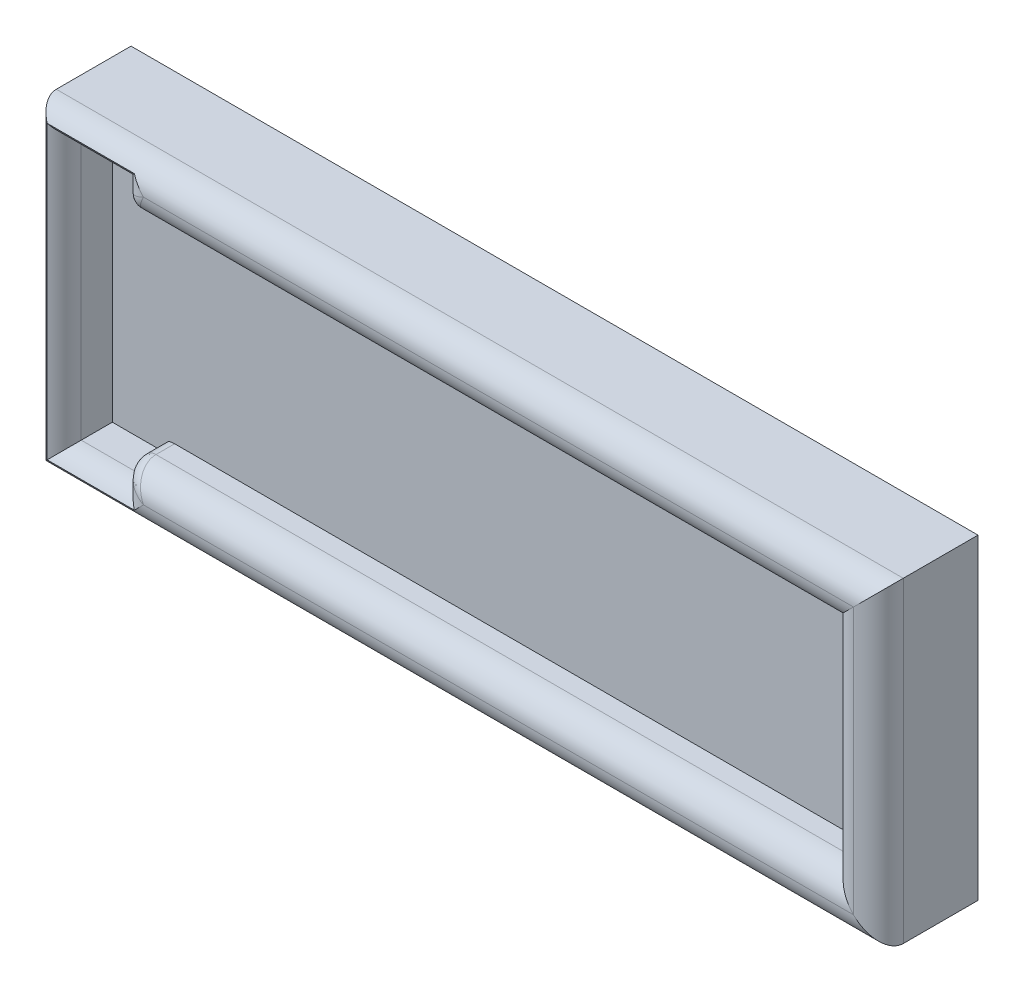
SolidWorks part; units mm, degrees
ref_plane "Спереди" through (0, 0, 0) normal (0, 0, 1) x (1, 0, 0)
ref_plane "Сверху" through (0, 0, 0) normal (0, 1, 0) x (1, 0, 0)
ref_plane "Справа" through (0, 0, 0) normal (1, 0, 0) x (0, 0, -1)
sketch "Эскиз1" plane through (0, 0, 0) normal (0, 0, 1) x (1, 0, 0)
  line L1 (17, -6.35) -> (-17, -6.35)
  line L2 (17, -6.35) -> (17, 6.35)
  line L3 (17, 6.35) -> (-17, 6.35)
  line L4 (-17, -6.35) -> (-17, 6.35)
  line L5 (0, 6.35) -> (0, -6.35) construction
  line L6 (17, 0) -> (-17, 0) construction
  point P0 (0, 0)
  dimension "D1" = 34
  dimension "D2" = 12.7
extrude "Бобышка-Вытянуть1" add sketch "Эскиз1" along normal mid plane 4
sketch "Эскиз3" plane through (0, 0, 0) normal (0, 0, 1) x (1, 0, 0)
  line L0 (-17, 6.35) -> (-17, -6.35) construction
  line L1 (16, -5.35) -> (-16, -5.35)
  line L2 (16, -5.35) -> (16, 5.35)
  line L3 (16, 5.35) -> (-16, 5.35)
  line L4 (-16, -5.35) -> (-16, 5.35)
  line L5 (0, 5.35) -> (0, -5.35) construction
  line L6 (16, 0) -> (-16, 0) construction
  line L7 (-17, -6.35) -> (17, -6.35) construction
  line L8 (17, 6.35) -> (-17, 6.35) construction
  line L9 (17, -6.35) -> (17, 6.35) construction
  point P0 (0, 0)
  dimension "D1" = 1
  dimension "D3" = 1
sketch "Эскиз7" plane through (0, 0, 0) normal (0, 1, 0) x (1, 0, 0)
  line L0 (-31.8558, 0) -> (37.696, 0) construction
  line L1 (0, 17.1372) -> (0, -14.6596) construction
  line L2 (11, 0.5) -> (16.5, 0.5)
  line L7 (14.5, -0.5) -> (16.5, 0.5)
  line L8 (17, 2) -> (-17, 2) construction
  line L9 (17, -2) -> (17, 2) construction
  line L10 (14.5, -0.5) -> (11, -0.5)
  line L12 (11, 0.5) -> (11, -0.5)
  dimension "D1" = 2.5
  dimension "D2" = 1.5
  dimension "D3" = 2
  dimension "D4" = 3.5
sweep "Вырез-По траектории1" cut profiles "Эскиз7" path "Эскиз3"
sketch "Эскиз2" plane through (0, 0, -0.5) normal (0, 0, 1) x (1, 0, 0)
  line L0 (17, -6.35) -> (17, 6.35) construction
  line L1 (15, -4.35) -> (-15, -4.35)
  line L2 (15, -4.35) -> (15, 4.35)
  line L3 (15, 4.35) -> (-15, 4.35)
  line L4 (-15, -4.35) -> (-15, 4.35)
  line L5 (0, 4.35) -> (0, -4.35) construction
  line L6 (15, 0) -> (-15, 0) construction
  line L7 (-17, -6.35) -> (17, -6.35) construction
  line L8 (17, 6.35) -> (-17, 6.35) construction
  line L9 (-17, 6.35) -> (-17, -6.35) construction
  point P0 (0, 0)
  dimension "D1" = 2
  dimension "D3" = 2
extrude "Вырез-Вытянуть3" cut sketch "Эскиз2" along normal through all
sketch "Эскиз4" plane through (0, 0, -0.5) normal (0, 0, 1) x (1, 0, 0)
  line L1 (-13.5, -5.35) -> (-16, -5.35)
  line L2 (-13.5, -5.35) -> (-13.5, 5.35)
  line L3 (-13.5, 5.35) -> (-16, 5.35)
  line L4 (-16, -5.35) -> (-16, 5.35)
  line L6 (-17, 6.35) -> (-17, -6.35) construction
  line L7 (-15, 4.35) -> (-15, -4.35) construction
  line L8 (17, 6.35) -> (-17, 6.35) construction
  point P9 (-16, 0)
  dimension "D1" = 1
  dimension "D2" = 1
  dimension "D3" = 1.5
extrude "Вырез-Вытянуть4" cut sketch "Эскиз4" along normal through all
fillet "Скругление1" radius 1 12 edges at (17, 0, 2) (0, 6.35, 2) (-17, 0, 2) (0, -6.35, 2) (-13.5, -4.85, 2) (0.75, -4.35, 2) (15, 0, 2) (0.75, 4.35, 2) (-13.5, 4.85, 2) (-16, 0, 2) (-14.75, -5.35, 2) (-14.75, 5.35, 2)
fillet "Скругление2" radius 0.5 4 edges at (-13.5, -4.35, 0.625) (-13.5, 4.35, 0.625) (-13.2071, -4.6429, 1.7071) (-13.2071, 4.6429, 1.7071)
sketch "Эскиз5" plane through (0, 0, 0) normal (1, 0, 0) x (0, 0, -1)
  line L0 (0.3, -7.75) -> (0.5, -7.75)
  line L1 (0.3, -7.75) -> (0.3, 7.75)
  line L2 (0.5, -7.75) -> (0.5, 7.75)
  line L3 (0.3, 7.75) -> (0.5, 7.75)
  line L4 (0.3, -7.75) -> (0.5, 7.75) construction
  line L5 (0.5, -7.75) -> (0.3, 7.75) construction
  point P1 (0.4, 0)
  dimension "D1" = 15.5
  dimension "D2" = 0.2
  dimension "D3" = 0.5
extrude "Вырез-Вытянуть5" [suppressed] cut sketch "Эскиз5" against normal through all
